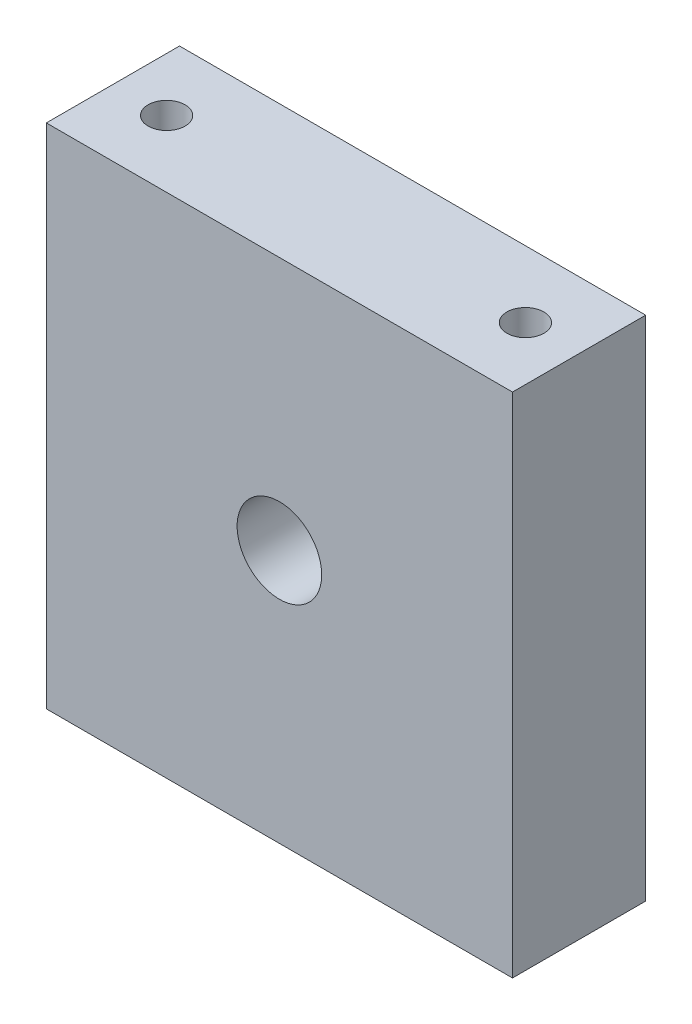
SolidWorks part; units mm, degrees
ref_plane "Front Plane" through (0, 0, 0) normal (0, 0, 1) x (1, 0, 0)
ref_plane "Top Plane" through (0, 0, 0) normal (0, 1, 0) x (1, 0, 0)
ref_plane "Right Plane" through (0, 0, 0) normal (1, 0, 0) x (0, 0, -1)
sketch "Sketch1" plane through (0, 0, 0) normal (0, 0, 1) x (1, 0, 0)
  line L1 (-17.5, 19.05) -> (17.5, 19.05)
  line L2 (-17.5, 19.05) -> (-17.5, -19.05)
  line L3 (-17.5, -19.05) -> (17.5, -19.05)
  line L4 (17.5, 19.05) -> (17.5, -19.05)
  point P4 (0, 19.05)
  point P6 (-17.5, 0)
  dimension "D1" = 38.1
  dimension "D2" = 35
extrude "Boss-Extrude1" add sketch "Sketch1" along normal blind 10
hole_wizard "7/64 (0.10938) Diameter Hole1" positions "Sketch2" profile "Sketch3" hole size "7/64" standard "ANSI Inch" end condition through all
sketch "Sketch2" plane through (0, 19.05, 0) normal (0, 1, 0) x (1, 0, 0)
  line L0 (-17.5, -10) -> (-17.5, 0) construction
  line L1 (-13.47, -5) -> (13.47, -5) construction
  point P0 (-13.47, -5)
  point P2 (13.47, -5)
  point P7 (-17.5, -5)
  point P12 (0, -5)
  dimension "D1" = 26.94
sketch "Sketch3" plane through (-13.47, 19.05, 5) normal (1, 0, 0) x (0, 0, 1)
  line L0 (0, 0) -> (0, 38.1)
  line L1 (0, 38.1) -> (1.3891, 38.1)
  line L2 (1.3891, 38.1) -> (1.3891, 0)
  line L5 (1.3891, 0) -> (0, 0)
  line L11 (0, -6.35) -> (0, 107.95) construction
  dimension "Thru Hole Dia." = 2.7783
  dimension "Thru Hole Depth" = 38.1
sketch "Sketch4" plane through (0, 0, 10) normal (0, 0, 1) x (1, 0, 0)
  line L0 (-17.5, -19.05) -> (17.5, -19.05) construction
  line L1 (17.5, 19.05) -> (-17.5, 19.05) construction
  circle A0 centre (0, 0) radius 3.175
  point P2 (0, 0)
  point P5 (0, 0)
  point P8 (0, 19.05)
  dimension "D1" = 6.35
  dimension "D2" = 19.05
extrude "Cut-Extrude1" cut sketch "Sketch4" against normal through all
